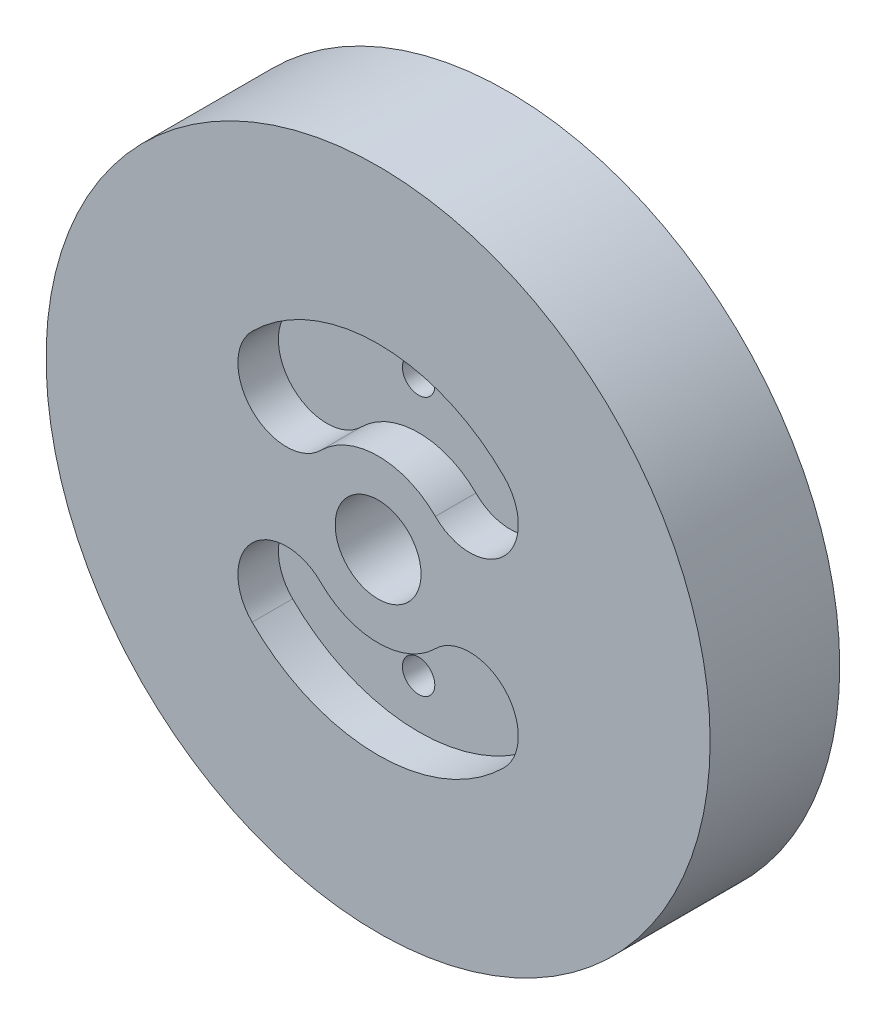
SolidWorks part; units mm, degrees
ref_plane "정면" through (0, 0, 0) normal (0, 0, 1) x (1, 0, 0)
ref_plane "윗면" through (0, 0, 0) normal (0, 1, 0) x (1, 0, 0)
ref_plane "우측면" through (0, 0, 0) normal (1, 0, 0) x (0, 0, -1)
sketch "스케치1" plane through (0, 0, 0) normal (0, 0, 1) x (1, 0, 0)
  circle A0 centre (0, 0) radius 20.5
  circle A1 centre (0, 0) radius 2.65
  point P4 (0, 0)
  dimension "D1" = 41
  dimension "D2" = 5.3
extrude "보스-돌출1" add sketch "스케치1" along normal blind 8 contours A0
extrude "컷-돌출1" cut sketch "스케치1<3>" along normal through all and the other way through all contours A1
sketch "스케치1<3>" plane through (0, 0, 0) normal (0, 0, 1) x (1, 0, 0) same geometry as "스케치1"
sketch "스케치9" plane through (0, 0, 8) normal (0, 0, 1) x (1, 0, 0)
  line L0 (0, 8) -> (0, 5) construction
  line L1 (0, 0) -> (6.2181, 0) construction
  circle A0 centre (0, 0) radius 8 construction
  arc A1 (-5.6569, 5.6569) -> (5.6569, 5.6569) centre (0, 0) cw construction
  arc A2 (7.7782, 7.7782) -> (-7.7782, 7.7782) centre (0, 0) ccw
  arc A3 (3.5355, 3.5355) -> (-3.5355, 3.5355) centre (0, 0) ccw
  arc A4 (3.5355, 3.5355) -> (7.7782, 7.7782) centre (5.6569, 5.6569) ccw
  arc A5 (-7.7782, 7.7782) -> (-3.5355, 3.5355) centre (-5.6569, 5.6569) ccw
  circle A7 centre (0, 8) radius 1
  circle A8 centre (0, -8) radius 1
  arc A9 (-5.6569, -5.6569) -> (5.6569, -5.6569) centre (0, 0) ccw construction
  arc A10 (7.7782, -7.7782) -> (-7.7782, -7.7782) centre (0, 0) cw
  arc A11 (3.5355, -3.5355) -> (-3.5355, -3.5355) centre (0, 0) cw
  arc A12 (3.5355, -3.5355) -> (7.7782, -7.7782) centre (5.6569, -5.6569) cw
  arc A13 (-7.7782, -7.7782) -> (-3.5355, -3.5355) centre (-5.6569, -5.6569) cw
  point P5 (0, 8)
  point P20 (0, -8)
  dimension "D1" = 5
  dimension "D2" = 11
  dimension "D3" = 16
  dimension "D4" = 90
  dimension "D5" = 2
extrude "컷-돌출2" cut sketch "스케치9" against normal blind 2.5 contours A2 A5 A3 A4 A7 | A13 A10 A12 A11 A8 region at (0, 6.7429, 8) region at (0, -6.7429, 8)
extrude "컷-돌출3" cut sketch "스케치9<3>" against normal through all contours A7 | A8 region at (0, 8, 8) region at (0, -8, 8)
sketch "스케치9<3>" plane through (0, 0, 8) normal (0, 0, 1) x (1, 0, 0) same geometry as "스케치9"
sketch "스케치12" plane through (0, 0, 0) normal (0, 0, -1) x (-1, 0, 0)
  circle A0 centre (-12.5, 0) radius 2.65
  circle A1 centre (12.5, 0) radius 2.65
  dimension "D1" = 5.3
  dimension "D2" = 5.3
  dimension "D3" = 25
  dimension "D4" = 12.5
extrude "컷-돌출4" cut sketch "스케치12" against normal blind 5 contours A0 | A1
